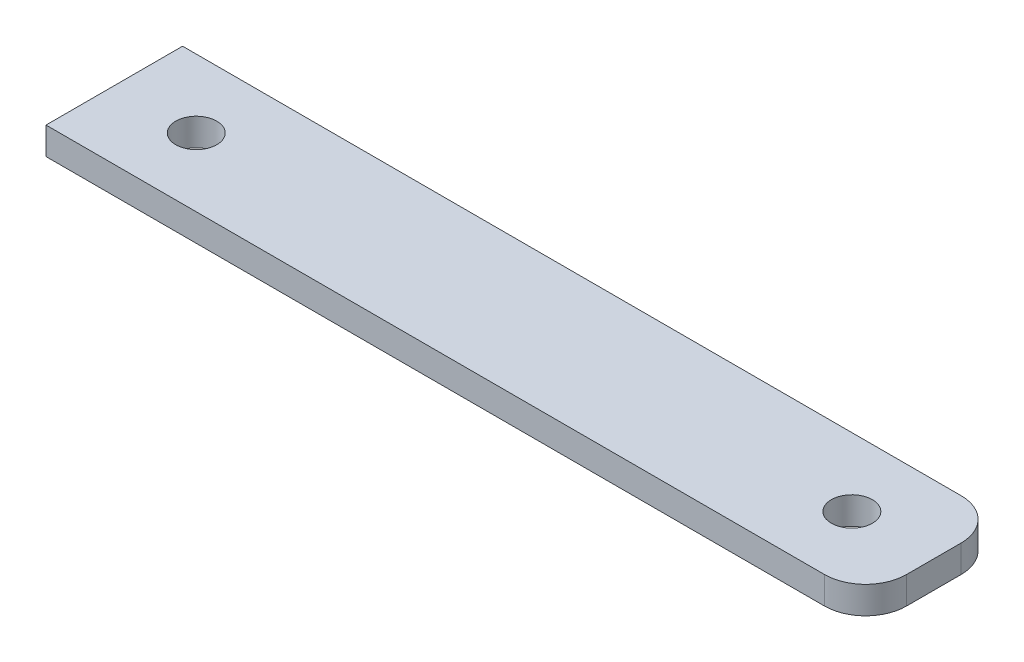
SolidWorks part; units mm, degrees
ref_plane "Front Plane" through (0, 0, 0) normal (0, 0, 1) x (1, 0, 0)
ref_plane "Top Plane" through (0, 0, 0) normal (0, 1, 0) x (1, 0, 0)
ref_plane "Right Plane" through (0, 0, 0) normal (1, 0, 0) x (0, 0, -1)
sketch "Sketch1" plane through (0, 0, 0) normal (0, 1, 0) x (1, 0, 0)
  line L1 (-30, 5) -> (30, 5)
  line L2 (-30, 5) -> (-30, -5)
  line L3 (-30, -5) -> (30, -5)
  line L4 (30, 5) -> (30, -5)
  line L5 (-30, 5) -> (30, -5) construction
  line L6 (-30, -5) -> (30, 5) construction
  point P0 (0, 0)
  dimension "D1" = 10
  dimension "D2" = 60
extrude "Boss-Extrude1" add sketch "Sketch1" along normal blind 2
sketch "Sketch2" plane through (0, 2, 0) normal (0, 1, 0) x (1, 0, 0)
  point P10 (26.3156, 0)
fillet "Fillet1" radius 3 2 edges at (30, 1, 5) (30, 1, -5)
hole_wizard "Ø3.0mm Dowel Hole1" positions "Sketch5" profile "Sketch6" hole size "Ø3.0" standard "ISO" end condition through all
sketch "Sketch5" plane through (0, 0, 0) normal (0, -1, 0) x (-1, 0, 0)
  line L0 (30, 5) -> (30, -5) construction
  line L1 (-30, -2) -> (-30, 2) construction
  point P0 (-24, 0)
  point P2 (24, 0)
  dimension "D1" = 6
  dimension "D2" = 6
sketch "Sketch6" plane through (24, 0, 0) normal (1, 0, 0) x (0, 0, -1)
  line L0 (0, 0) -> (0, 2)
  line L1 (0, 2) -> (1.5, 2)
  line L2 (1.5, 2) -> (1.5, 0)
  line L5 (1.5, 0) -> (0, 0)
  line L11 (0, -6.35) -> (0, 107.95) construction
  dimension "Thru Hole Dia." = 3
  dimension "Thru Hole Depth" = 2
